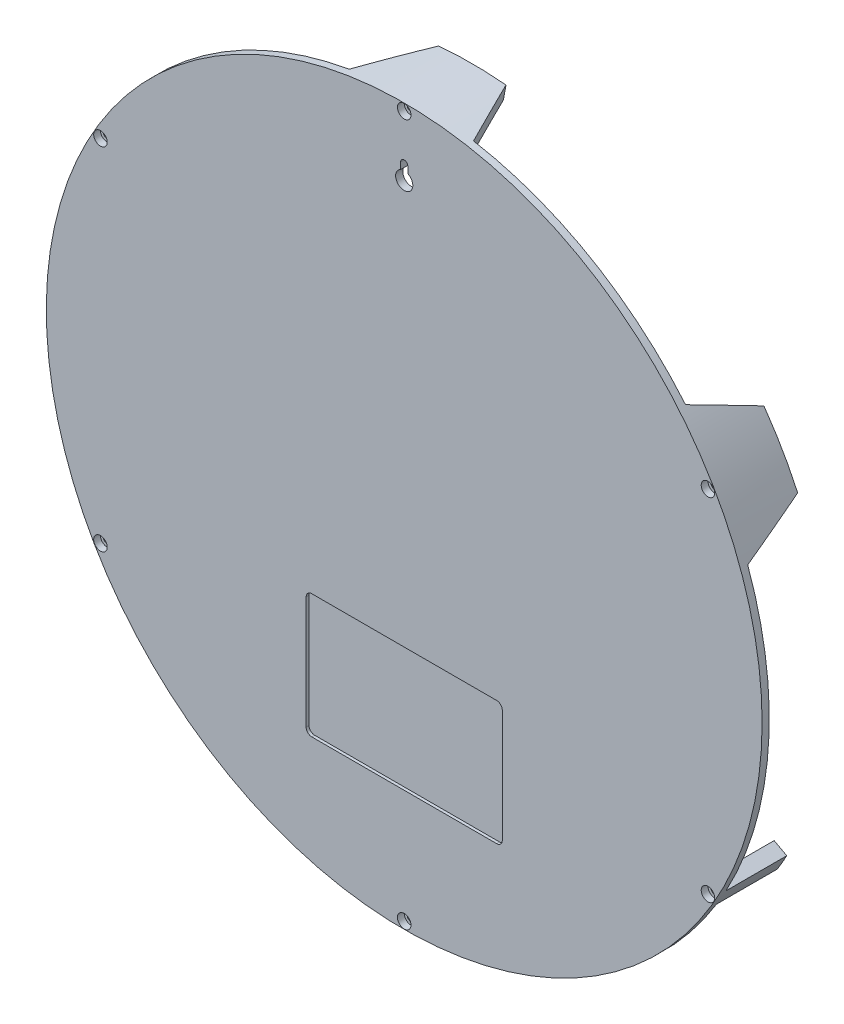
SolidWorks part; units mm, degrees
ref_plane "Front Plane" through (0, 0, 0) normal (0, 0, 1) x (1, 0, 0)
ref_plane "Top Plane" through (0, 0, 0) normal (0, 1, 0) x (1, 0, 0)
ref_plane "Right Plane" through (0, 0, 0) normal (1, 0, 0) x (0, 0, -1)
sketch "Sketch1" plane through (0, 0, 0) normal (0, 0, 1) x (1, 0, 0)
  circle A0 centre (0, 0) radius 158.75
  dimension "D1" = 317.5
extrude "Boss-Extrude1" add sketch "Sketch1" along normal blind 3.175
sketch "Sketch2" plane through (0, 0, 3.175) normal (0, 0, 1) x (1, 0, 0)
  line L0 (0, 0) -> (0, 155.575) construction
  circle A0 centre (0, 0) radius 155.575
  point P4 (0, 155.575)
  dimension "D1" = 311.15
sketch "Sketch4" plane through (0, 0, 0) normal (0, 1, 0) x (1, 0, 0)
  line L0 (0, 0) -> (0, 25.4) construction
  dimension "D1" = 25.4
sketch "Sketch9" plane through (0, 0, 0) normal (0, 0, -1) x (-1, 0, 0)
  line L0 (-27.5666, 156.3382) -> (-26.464, 150.0847)
  line L1 (26.464, 150.0847) -> (27.5666, 156.3382)
  line L2 (0, 158.75) -> (0, 0) construction
  circle A1 centre (0, 0) radius 158.75 construction
  circle A2 centre (0, 0) radius 152.4
  arc A3 (26.464, 150.0847) -> (-26.464, 150.0847) centre (0, 0) ccw
  arc A4 (27.5666, 156.3382) -> (-27.5666, 156.3382) centre (0, 0) ccw
  dimension "D2" = 20
  dimension "D1" = 6.35
extrude "Boss-Extrude2" add sketch "Sketch9" along normal blind 26.9875 contours A3 L0 A4 L1
chamfer "Chamfer1" distance 26.9875 distance2 12.7 2 edges at (27.0153, 153.2115, -26.9875) (-27.0153, 153.2115, -26.9875)
hole_wizard "CBORE for M3 SHCS1" positions "Sketch2" profile "Sketch6" counterbore size "M3" standard "ANSI Metric" end condition through all
sketch "Sketch6" plane through (0, 155.575, 3.175) normal (1, 0, 0) x (0, -1, 0)
  line L0 (0, 0) -> (0, 30.1625)
  line L1 (0, 30.1625) -> (1.7, 30.1625)
  line L3 (1.7, 30.1625) -> (1.7, 3)
  line L4 (1.7, 3) -> (3, 3)
  line L5 (3, 3) -> (3, 0)
  line L7 (3, 0) -> (0, 0)
  line L11 (0, -6.35) -> (0, 107.95) construction
  dimension "Thru Hole Dia." = 3.4
  dimension "Thru Hole Depth" = 30.1625
  dimension "C'Bore Dia." = 6
  dimension "C'Bore Depth" = 3
pattern_circular "CirPattern1" count 6 over 360 about axis through (0, 0, 0) along (0, 0, 1) of "CBORE for M3 SHCS1", "Boss-Extrude2", "Chamfer1"
sketch "Sketch7" plane through (0, 0, 3.175) normal (0, 0, 1) x (1, 0, 0)
  line L0 (0, 0) -> (0, 155.575) construction
  line L1 (0, 128.905) -> (0, 135.255) construction
  line L2 (-1.5875, 132.3685) -> (-1.5875, 135.255)
  line L3 (1.5875, 132.3685) -> (1.5875, 135.255)
  arc A0 (-1.5875, 132.3685) -> (1.5875, 132.3685) centre (0, 128.905) ccw
  arc A2 (1.5875, 135.255) -> (-1.5875, 135.255) centre (0, 135.255) ccw
  point P6 (0, 140.335)
  dimension "D1" = 7.62
  dimension "D3" = 1.5875
  dimension "D2" = 26.67
  dimension "D4" = 6.35
extrude "Cut-Extrude1" cut sketch "Sketch7" along a picked direction on the side against the normal blind 3.175
sketch "Sketch8" plane through (0, 0, 3.175) normal (0, 0, 1) x (1, 0, 0)
  line L0 (0, 0) -> (0, -155.575) construction
  line L1 (-43, -50.775) -> (43, -50.775)
  line L2 (-43, -50.775) -> (-43, -104.775)
  line L3 (-43, -104.775) -> (43, -104.775)
  line L4 (43, -50.775) -> (43, -104.775)
  point P8 (0, -50.775)
  point P9 (0, -104.775)
  dimension "D1" = 86
  dimension "D2" = 54
  dimension "D3" = 50.8
extrude "Cut-Extrude2" cut sketch "Sketch8" against normal blind 1.27 contours L1 L4 L3 L2
fillet "Fillet1" radius 2 4 edges at (-43, -104.775, 2.54) (43, -104.775, 2.54) (43, -50.775, 2.54) (-43, -50.775, 2.54)
sketch "Sketch13" plane through (0, 0, 3.175) normal (0, 0, 1) x (1, 0, 0)
  line L14 (-43.5, -52.775) -> (-43.5, -102.775)
  line L15 (-41, -105.275) -> (41, -105.275)
  line L16 (43.5, -102.775) -> (43.5, -52.775)
  line L17 (41, -50.275) -> (-41, -50.275)
  line L18 (-43.5, -52.775) -> (-43.5, -102.775)
  line L19 (-41, -105.275) -> (41, -105.275)
  line L20 (43.5, -102.775) -> (43.5, -52.775)
  line L21 (41, -50.275) -> (-41, -50.275)
  arc A9 (-43.5, -102.775) -> (-41, -105.275) centre (-41, -102.775) ccw
  arc A10 (41, -105.275) -> (43.5, -102.775) centre (41, -102.775) ccw
  arc A11 (43.5, -52.775) -> (41, -50.275) centre (41, -52.775) ccw
  arc A12 (-41, -50.275) -> (-43.5, -52.775) centre (-41, -52.775) ccw
  arc A13 (-43.5, -102.775) -> (-41, -105.275) centre (-41, -102.775) ccw
  arc A14 (41, -105.275) -> (43.5, -102.775) centre (41, -102.775) ccw
  arc A15 (43.5, -52.775) -> (41, -50.275) centre (41, -52.775) ccw
  arc A16 (-41, -50.275) -> (-43.5, -52.775) centre (-41, -52.775) ccw
  dimension "D1" = 0.5
extrude "Cut-Extrude4" cut sketch "Sketch13" against normal up to surface (1.27 mm away) up to face at (0, -77.775, 1.905)
sketch "Sketch10" plane through (0, 0, -26.9875) normal (0, 0, -1) x (-1, 0, 0)
  line L0 (-139.5122, -75.749) -> (-133.9317, -72.719)
  line L1 (-135.3566, -82.9466) -> (-129.9424, -79.6288)
  line L2 (-137.4815, -79.375) -> (-131.9823, -76.2) construction
  line L3 (-143.2092, -52.1239) -> (-149.1762, -54.2957) construction
  line L4 (-121.6096, -102.0425) -> (-116.7452, -97.9608) construction
  line L5 (-129.3832, -91.9867) -> (-124.5025, -87.8913)
  line L6 (-138.3674, -63.8767) -> (-144.3544, -66.0558)
  line L7 (-121.6096, -102.0425) -> (-116.7452, -97.9608)
  line L8 (-143.2092, -52.1239) -> (-149.1762, -54.2957)
  arc A0 (-144.3544, -66.0558) -> (-129.3832, -91.9867) centre (0, 0) ccw construction
  arc A1 (-143.2092, -52.1239) -> (-116.7452, -97.9608) centre (0, 0) ccw construction
  arc A2 (-138.3674, -63.8767) -> (-124.5025, -87.8913) centre (0, 0) ccw construction
  arc A5 (-144.3544, -66.0558) -> (-129.3832, -91.9867) centre (0, 0) ccw
  arc A6 (-138.3674, -63.8767) -> (-124.5025, -87.8913) centre (0, 0) ccw
  arc A7 (-149.1762, -54.2957) -> (-121.6096, -102.0425) centre (0, 0) ccw
  arc A8 (-143.2092, -52.1239) -> (-116.7452, -97.9608) centre (0, 0) ccw
  arc M9 (-144.3544, -66.0558) -> (-129.3832, -91.9867) centre (0, 0) ccw
  line M10 (-129.3832, -91.9867) -> (-124.5025, -87.8913)
  arc M11 (-124.5025, -87.8913) -> (-138.3674, -63.8767) centre (0, 0) cw
  line M12 (-138.3674, -63.8767) -> (-144.3544, -66.0558)
  dimension "D2" = 3
  dimension "D1" = 0
extrude "Cut-Extrude3" cut sketch "Sketch10" against normal up to surface (26.9875 mm away) contours L0 M9 M11 M12 | L1 M9 M10 M11 | A8 L8 A7 M12 | A8 A7 L7 M10 up to face at (0, 132.3903, 0)
sketch "Sketch11" plane through (0, 0, 0) normal (1, 0, 0) x (0, 0, -1)
  line L4 (26.9875, 152.4) -> (0, 152.4)
  line L5 (26.9875, 152.4) -> (0, 152.4)
  line L6 (26.9875, 152.4) -> (0, 139.7)
  line L7 (0, 139.7) -> (0, 152.4)
  dimension "D1" = 12.7
extrude "Boss-Extrude3" add sketch "Sketch11" along normal mid plane 6.35
chamfer "Chamfer2" distance 2 angle 45 7 edges at (131.9823, -76.2, 0) (0, -152.4, 0) (-131.9823, -76.2, 0) (-131.9823, 76.2, 0) (-14.8634, 151.6735, 0) (14.8634, 151.6735, 0) (131.9823, 76.2, 0)
